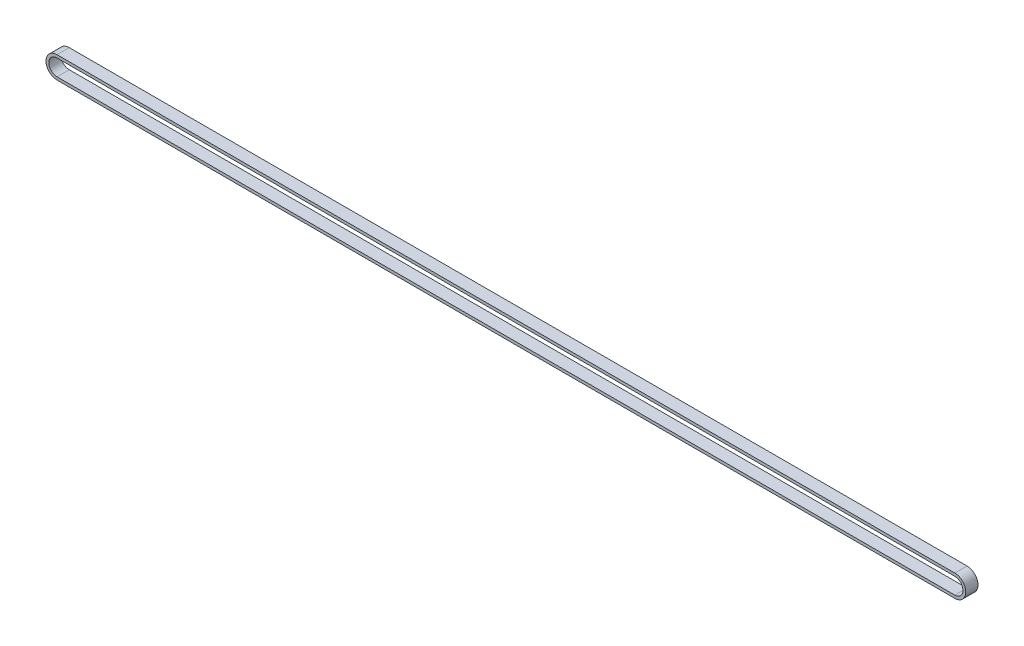
SolidWorks part; units mm, degrees
ref_plane "Front Plane" through (0, 0, 0) normal (0, 0, 1) x (1, 0, 0)
ref_plane "Top Plane" through (0, 0, 0) normal (0, 1, 0) x (1, 0, 0)
ref_plane "Right Plane" through (0, 0, 0) normal (1, 0, 0) x (0, 0, -1)
sketch "Sketch1" plane through (0, 0, 0) normal (0, 0, 1) x (1, 0, 0)
  line L0 (-220, 5.38) -> (220, 5.38)
  line L1 (-220, -4) -> (220, -4)
  line L3 (-220, 4) -> (220, 4)
  line L5 (-220, -4) -> (220, 4) construction
  line L6 (-220, 4) -> (220, -4) construction
  line L7 (-220, -5.38) -> (220, -5.38)
  arc A0 (-220, 4) -> (-220, -4) centre (-220, 0) ccw
  arc A1 (220, -4) -> (220, 4) centre (220, 0) ccw
  arc A2 (220, -5.38) -> (220, 5.38) centre (220, 0) ccw
  arc A3 (-220, 5.38) -> (-220, -5.38) centre (-220, 0) ccw
  point P0 (0, 0)
  dimension "D1" = 4
  dimension "D2" = 440
  dimension "D3" = 1.38
extrude "Boss-Extrude1" add sketch "Sketch1" along normal blind 6
